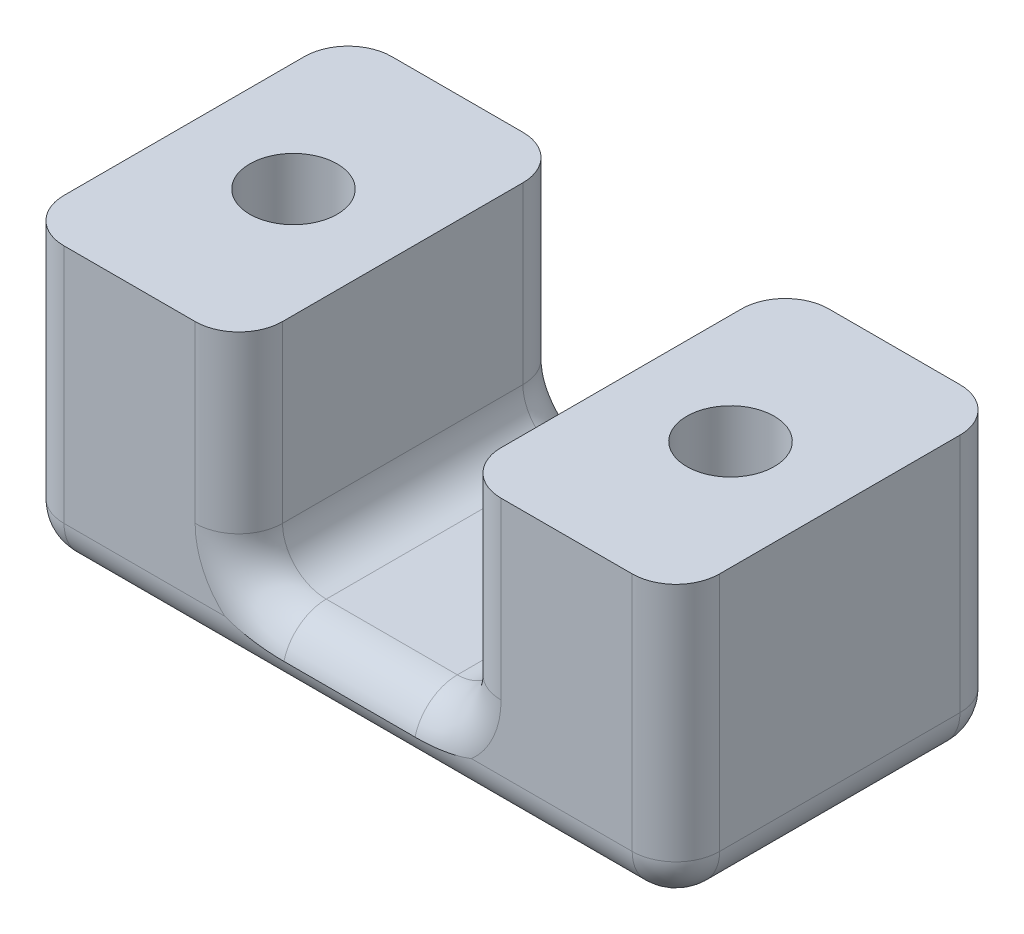
SolidWorks part; units mm, degrees
ref_plane "Front Plane" through (0, 0, 0) normal (0, 0, 1) x (1, 0, 0)
ref_plane "Top Plane" through (0, 0, 0) normal (0, 1, 0) x (1, 0, 0)
ref_plane "Right Plane" through (0, 0, 0) normal (1, 0, 0) x (0, 0, -1)
sketch "Sketch1" plane through (0, 0, 0) normal (0, 1, 0) x (1, 0, 0)
  line L1 (0, 0) -> (30, 0)
  line L2 (0, 0) -> (0, 15)
  line L3 (0, 15) -> (30, 15)
  line L4 (30, 0) -> (30, 15)
  dimension "D1" = 30
  dimension "D2" = 15
extrude "Boss-Extrude1" add sketch "Sketch1" along normal blind 3
sketch "Sketch2" plane through (0, 3, 0) normal (0, 1, 0) x (1, 0, 0)
  line L0 (0, 0) -> (30, 0) construction
  line L1 (0, 15) -> (10, 15)
  line L2 (0, 15) -> (0, 0)
  line L3 (0, 0) -> (10, 0)
  line L4 (10, 15) -> (10, 0)
  line L6 (30, 15) -> (20, 15)
  line L7 (30, 15) -> (30, 0)
  line L8 (30, 0) -> (20, 0)
  line L9 (20, 15) -> (20, 0)
  dimension "D1" = 10
extrude "Boss-Extrude2" add sketch "Sketch2" along normal blind 10
sketch "Sketch3" plane through (0, 0, 0) normal (0, -1, 0) x (1, 0, 0)
  line L0 (0, -7.5) -> (30, -7.5) construction
  line L1 (0, -15) -> (0, 0) construction
  line L2 (30, 0) -> (30, -15) construction
  line L3 (5, 0) -> (5, -15) construction
  line L4 (0, 0) -> (30, 0) construction
  line L5 (30, -15) -> (0, -15) construction
  line L6 (15, 0) -> (15, -15) construction
  circle A0 centre (5, -7.5) radius 2
  circle A1 centre (25, -7.5) radius 2
  dimension "D2" = 4
  dimension "D1" = 5
extrude "Cut-Extrude1" cut sketch "Sketch3" against normal blind 30
fillet "Fillet1" radius 2 16 edges at (15, 0, 0) (30, 0, -7.5) (15, 0, -15) (0, 0, -7.5) (10, 8, 0) (20, 8, 0) (10, 8, -15) (20, 8, -15) (30, 6.5, 0) (30, 6.5, -15) (0, 6.5, -15) (0, 6.5, 0) (15, 3, 0) (10, 3, -7.5) (15, 3, -15) (20, 3, -7.5)
